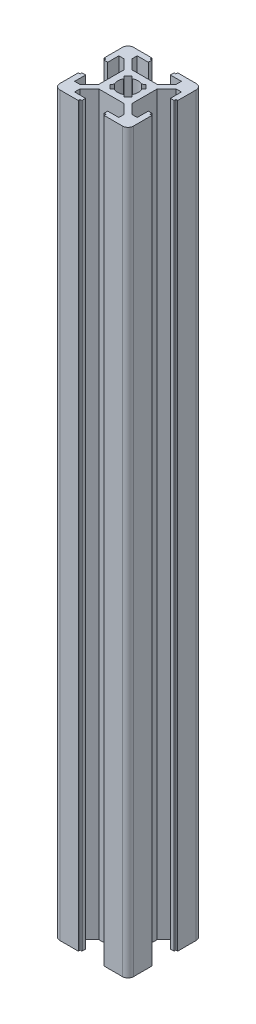
SolidWorks part; units mm, degrees
material "3.3547 (EN-AW 5083)"
ref_plane "Płaszczyzna przednia" through (0, 0, 0) normal (0, 0, 1) x (1, 0, 0)
ref_plane "Płaszczyzna górna" through (0, 0, 0) normal (0, 1, 0) x (1, 0, 0)
ref_plane "Płaszczyzna prawa" through (0, 0, 0) normal (1, 0, 0) x (0, 0, -1)
sketch "Szkic1" plane through (0, 0, 0) normal (0, 1, 0) x (1, 0, 0)
  line L0 (0, 10) -> (0, -10) construction
  line L1 (4.5, -4.5) -> (-4.5, -4.5)
  line L2 (4.5, -4.5) -> (4.5, 4.5)
  line L3 (4.5, 4.5) -> (-4.5, 4.5)
  line L4 (-4.5, -4.5) -> (-4.5, 4.5)
  line L5 (4.5, -4.5) -> (-4.5, 4.5) construction
  line L6 (4.5, 4.5) -> (-4.5, -4.5) construction
  line L7 (8.5, -10) -> (-8.5, -10)
  line L8 (10, -8.5) -> (10, 8.5)
  line L9 (8.5, 10) -> (-8.5, 10)
  line L10 (-10, -8.5) -> (-10, 8.5)
  line L11 (10, -10) -> (-10, 10) construction
  line L12 (10, 10) -> (-10, -10) construction
  line L13 (3.5, 10) -> (-3.5, 10)
  line L14 (-3.5, 10) -> (-3.5, 9.5)
  line L15 (-3.5, 9.5) -> (-3, 9.5)
  line L16 (-3, 9.5) -> (-3, 8.5)
  line L17 (-3, 8.5) -> (-6, 8.5)
  line L18 (-6, 8.5) -> (-6, 7.06)
  line L19 (-6, 7.06) -> (-3.4405, 4.5)
  line L20 (-1.9445, 3.0052) -> (-3.0052, 1.9445)
  line L21 (-1.9445, 3.0052) -> (-1.2713, 2.4385)
  line L22 (-3.0052, 1.9445) -> (-2.4385, 1.2713)
  line L23 (3.5, 10) -> (3.5, 9.5)
  line L24 (3.5, 9.5) -> (3, 9.5)
  line L25 (3, 9.5) -> (3, 8.5)
  line L26 (3, 8.5) -> (6, 8.5)
  line L27 (6, 8.5) -> (6, 7.06)
  line L28 (6, 7.06) -> (3.4405, 4.5)
  line L29 (1.9445, 3.0052) -> (3.0052, 1.9445)
  line L30 (1.9445, 3.0052) -> (1.2713, 2.4385)
  line L31 (3.0052, 1.9445) -> (2.4385, 1.2713)
  line L32 (1.9445, 3.0052) -> (1.2713, 2.4385)
  line L33 (3.0052, 1.9445) -> (1.9445, 3.0052)
  line L34 (3.0052, 1.9445) -> (2.4385, 1.2713)
  line L35 (7.06, 6) -> (4.5, 3.4405)
  line L36 (8.5, 6) -> (7.06, 6)
  line L37 (8.5, 3) -> (8.5, 6)
  line L38 (9.5, 3) -> (8.5, 3)
  line L39 (9.5, 3.5) -> (9.5, 3)
  line L40 (10, 3.5) -> (9.5, 3.5)
  line L41 (10, -3.5) -> (9.5, -3.5)
  line L42 (9.5, -3.5) -> (9.5, -3)
  line L43 (9.5, -3) -> (8.5, -3)
  line L44 (8.5, -3) -> (8.5, -6)
  line L45 (8.5, -6) -> (7.06, -6)
  line L46 (7.06, -6) -> (4.5, -3.4405)
  line L47 (3.0052, -1.9445) -> (2.4385, -1.2713)
  line L48 (3.0052, -1.9445) -> (1.9445, -3.0052)
  line L49 (1.9445, -3.0052) -> (1.2713, -2.4385)
  line L50 (3.0052, -1.9445) -> (2.4385, -1.2713)
  line L51 (1.9445, -3.0052) -> (3.0052, -1.9445)
  line L52 (1.9445, -3.0052) -> (1.2713, -2.4385)
  line L53 (6, -7.06) -> (3.4405, -4.5)
  line L54 (6, -8.5) -> (6, -7.06)
  line L55 (3, -8.5) -> (6, -8.5)
  line L56 (3, -9.5) -> (3, -8.5)
  line L57 (3.5, -9.5) -> (3, -9.5)
  line L58 (3.5, -10) -> (3.5, -9.5)
  line L59 (-3.5, -10) -> (-3.5, -9.5)
  line L60 (-3.5, -9.5) -> (-3, -9.5)
  line L61 (-3, -9.5) -> (-3, -8.5)
  line L62 (-3, -8.5) -> (-6, -8.5)
  line L63 (-6, -8.5) -> (-6, -7.06)
  line L64 (-6, -7.06) -> (-3.4405, -4.5)
  line L65 (-1.9445, -3.0052) -> (-1.2713, -2.4385)
  line L66 (-1.9445, -3.0052) -> (-3.0052, -1.9445)
  line L67 (-3.0052, -1.9445) -> (-2.4385, -1.2713)
  line L68 (-1.9445, -3.0052) -> (-1.2713, -2.4385)
  line L69 (-3.0052, -1.9445) -> (-1.9445, -3.0052)
  line L70 (-3.0052, -1.9445) -> (-2.4385, -1.2713)
  line L71 (-7.06, -6) -> (-4.5, -3.4405)
  line L72 (-8.5, -6) -> (-7.06, -6)
  line L73 (-8.5, -3) -> (-8.5, -6)
  line L74 (-9.5, -3) -> (-8.5, -3)
  line L75 (-9.5, -3.5) -> (-9.5, -3)
  line L76 (-10, -3.5) -> (-9.5, -3.5)
  line L77 (-10, 3.5) -> (-9.5, 3.5)
  line L78 (-9.5, 3.5) -> (-9.5, 3)
  line L79 (-9.5, 3) -> (-8.5, 3)
  line L80 (-8.5, 3) -> (-8.5, 6)
  line L81 (-8.5, 6) -> (-7.06, 6)
  line L82 (-7.06, 6) -> (-4.5, 3.4405)
  line L83 (-3.0052, 1.9445) -> (-2.4385, 1.2713)
  line L84 (-3.0052, 1.9445) -> (-1.9445, 3.0052)
  line L85 (-1.9445, 3.0052) -> (-1.2713, 2.4385)
  circle A0 centre (0, 0) radius 2.75
  arc A1 (10, -8.5) -> (8.5, -10) centre (8.5, -8.5) cw
  arc A2 (-10, -8.5) -> (-8.5, -10) centre (-8.5, -8.5) ccw
  arc A3 (10, 8.5) -> (8.5, 10) centre (8.5, 8.5) ccw
  arc A4 (-8.5, 10) -> (-10, 8.5) centre (-8.5, 8.5) ccw
  point P16 (0, 10)
  point P37 (-2.4749, 2.4749)
  dimension "D1" = 5.5
  dimension "D12" = 1.5
  dimension "D2" = 9
  dimension "D3" = 20
  dimension "D4" = 20
  dimension "D5" = 7
  dimension "D6" = 0.5
  dimension "D7" = 0.5
  dimension "D8" = 1
  dimension "D9" = 3
  dimension "D10" = 1.44
  dimension "D11" = 3.62
  dimension "D13" = 1.5
  dimension "D14" = 3.5
  dimension "D15" = 0.88
  dimension "D16" = 4
extrude "Dodanie-wyciągnięcie1" add sketch "Szkic1" along normal blind 807 contours L9 A4 L10 L77 L78 L79 L80 L81 L82 L4 L3 L19 L18 L17 L16 L15 L14 | L8 A3 L9 L23 L24 L25 L26 L27 L28 L3 L2 L35 L36 L37 L38 L39 L40 | L4 L1 L2 L3 A0 L47 L48 L49 L65 L66 L67 L22 L20 L21 L30 L29 L31 | L10 A2 L7 L59 L60 L61 L62 L63 L64 L1 L4 L71 L72 L73 L74 L75 L76 | A1 L8 L41 L42 L43 L44 L45 L46 L2 L1 L53 L54 L55 L56 L57 L58 L7 region at (7.2228, 0, 7.2228) region at (3.9703, 0, 4.3727) region at (-7.2228, 0, 7.2228) region at (7.2228, 0, -7.2228) region at (-7.2228, 0, -7.2228)
sketch "Skizze1" plane through (0, 0, 0) normal (0, 0, 1) x (1, 0, 0)
  line L0 (-83.4963, 200) -> (63.9108, 200)
  line L1 (63.9108, 200) -> (55.1488, 860.7548)
  line L2 (55.1488, 860.7548) -> (-83.4963, 858.9163)
  line L3 (-83.4963, 858.9163) -> (-83.4963, 200)
  dimension "D1" = 200
extrude "Schnitt-Linear austragen1" cut sketch "Skizze1" against normal mid plane 40
other "Freeze***"
